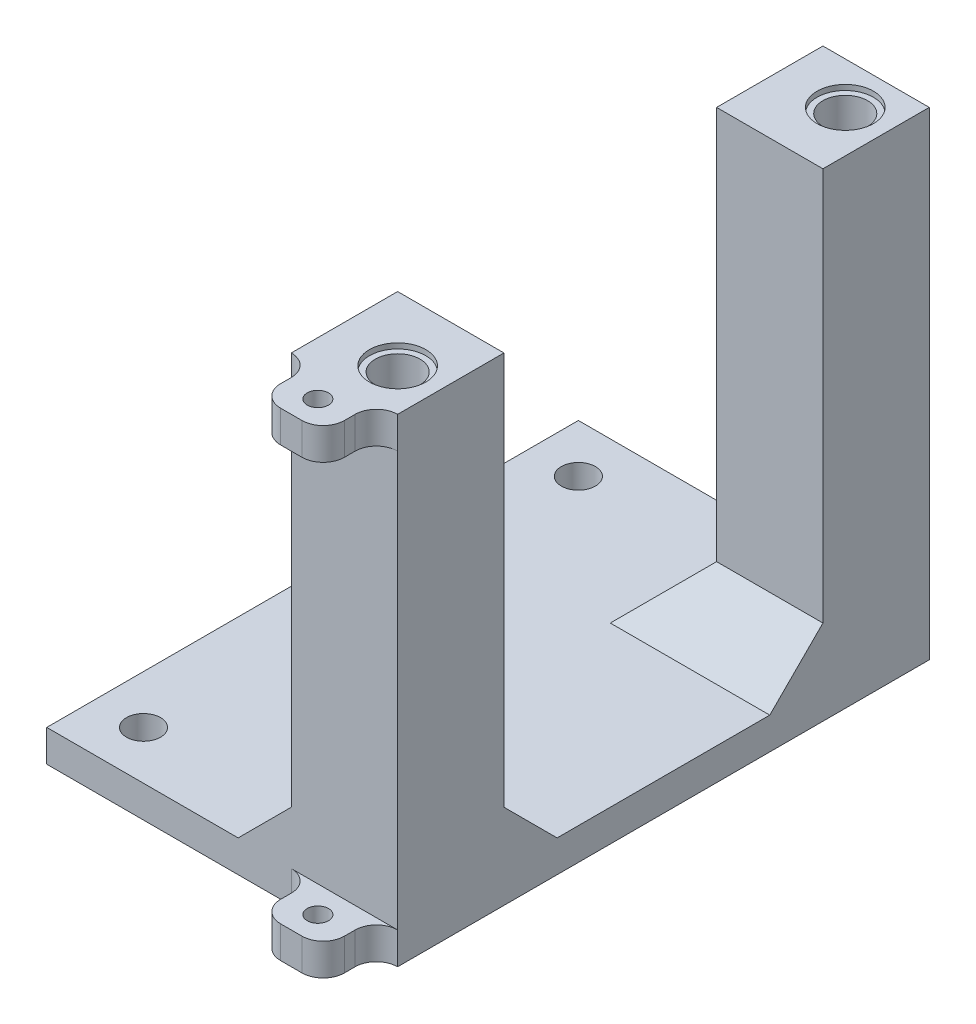
SolidWorks part; units mm, degrees
ref_plane "Front Plane" through (0, 0, 0) normal (0, 0, 1) x (1, 0, 0)
ref_plane "Top Plane" through (0, 0, 0) normal (0, 1, 0) x (1, 0, 0)
ref_plane "Right Plane" through (0, 0, 0) normal (1, 0, 0) x (0, 0, -1)
sketch "Sketch1" plane through (0, 0, 0) normal (0, 1, 0) x (1, 0, 0)
  line L1 (-6.5124, 9.686) -> (1.4876, 9.686)
  line L2 (-6.5124, 9.686) -> (-6.5124, -40.314)
  line L3 (-6.5124, -40.314) -> (1.4876, -40.314)
  line L4 (1.4876, 9.686) -> (1.4876, -40.314)
  line L5 (1.4876, 9.686) -> (26.4876, 9.686)
  line L6 (1.4876, 9.686) -> (1.4876, -40.314)
  line L7 (1.4876, -40.314) -> (26.4876, -40.314)
  line L8 (26.4876, 9.686) -> (26.4876, -40.314)
  circle A0 centre (-1.9624, -35.764) radius 1.6
  circle A1 centre (-1.9624, 5.136) radius 1.6
  dimension "D4" = 3.2
  dimension "D5" = 3.2
  dimension "D6" = 4.55
  dimension "D7" = 4.55
  dimension "D8" = 4.55
  dimension "D9" = 4.55
  dimension "D1" = 8
  dimension "D2" = 50
  dimension "D3" = 25
extrude "Boss-Extrude1" add sketch "Sketch1" along normal blind 3 contours A1 | A0 | L5 L8 L7 L3 L2 L1
sketch "Sketch2" plane through (0, 3, 0) normal (0, 1, 0) x (1, 0, 0)
  line L1 (26.4876, -40.314) -> (16.4876, -40.314)
  line L2 (26.4876, -40.314) -> (26.4876, -30.314)
  line L3 (26.4876, -30.314) -> (16.4876, -30.314)
  line L4 (16.4876, -40.314) -> (16.4876, -30.314)
  line L5 (26.4876, 9.686) -> (16.4876, 9.686)
  line L6 (26.4876, 9.686) -> (26.4876, -0.314)
  line L7 (26.4876, -0.314) -> (16.4876, -0.314)
  line L8 (16.4876, 9.686) -> (16.4876, -0.314)
  dimension "D1" = 10
  dimension "D2" = 10
  dimension "D3" = 10
  dimension "D4" = 10
extrude "Boss-Extrude2" add sketch "Sketch2" along normal blind 42
chamfer "Chamfer1" distance 5 angle 45 4 edges at (16.4876, 3, -4.686) (21.4876, 3, 0.314) (16.4876, 3, 35.314) (21.4876, 3, 30.314)
ref_plane "Plane1" through (0, 45, 0) normal (0, 1, 0) x (1, 0, 0)
sketch "Sketch3" plane through (0, 45, 0) normal (0, 1, 0) x (1, 0, 0)
  line L0 (26.4876, -40.314) -> (26.4876, -30.314) construction
  line L1 (16.4876, -40.314) -> (26.4876, -40.314) construction
  line L2 (26.4876, -0.314) -> (26.4876, 9.686) construction
  line L3 (26.4876, 9.686) -> (16.4876, 9.686) construction
  circle A0 centre (22.5376, -36.364) radius 2.1
  circle A1 centre (22.5376, 5.736) radius 2.1
  dimension "D1" = 4.2
  dimension "D3" = 3.95
  dimension "D4" = 4.2
  dimension "D6" = 3.95
  dimension "D2" = 3.95
  dimension "D5" = 3.95
extrude "Cut-Extrude1" cut sketch "Sketch3" against normal blind 52
sketch "Sketch4" plane through (0, 45, 0) normal (0, 1, 0) x (1, 0, 0)
  circle A0 centre (22.5376, -36.364) radius 2.65
  circle A1 centre (22.5376, 5.736) radius 2.65
  dimension "D1" = 5.3
  dimension "D2" = 5.3
extrude "Cut-Extrude2" cut sketch "Sketch4" against normal blind 0.5
ref_plane "Plane2" through (0, 22.5, 0) normal (0, -1, 0) x (-1, 0, 0)
mirror "Mirror1" about plane through (0, 22.5, 0) normal (0, -1, 0) of "Cut-Extrude2"
sketch "Sketch5" plane through (0, 0, -9.686) normal (0, 0, -1) x (-1, 0, 0)
  line L0 (-22.4876, 36.5) -> (-17.9876, 36.5) construction
  line L1 (-18.2876, 36.2) -> (-22.2399, 36.2)
  line L2 (-18.2876, 36.2) -> (-18.2876, 31.6868)
  line L3 (-18.2876, 31.6868) -> (-22.2399, 31.6868)
  line L4 (-22.2399, 36.2) -> (-22.2399, 31.6868)
  line L5 (-17.9876, 32.25) -> (-17.9876, 37) construction
  dimension "D1" = 0.3
  dimension "D2" = 0.3
sketch "Sketch11" plane through (0, 0, 40.314) normal (0, 0, 1) x (1, 0, 0)
  line L0 (16.4876, 45) -> (26.4876, 45) construction
  line L1 (18.4876, 45) -> (24.4876, 45)
  line L2 (18.4876, 45) -> (18.4876, 42)
  line L3 (18.4876, 42) -> (24.4876, 42)
  line L4 (24.4876, 45) -> (24.4876, 42)
  line L5 (-6.5124, 0) -> (26.4876, 0) construction
  line L6 (18.4876, 0) -> (24.4876, 0)
  line L7 (18.4876, 0) -> (18.4876, 3)
  line L8 (18.4876, 3) -> (24.4876, 3)
  line L9 (24.4876, 0) -> (24.4876, 3)
  line L10 (21.4876, 8) -> (21.4876, 0) construction
  line L11 (21.4876, 8) -> (21.4876, 45) construction
  line L13 (-6.5124, 3) -> (11.4876, 3) construction
  line L14 (16.4876, 8) -> (26.4876, 8) construction
  line L15 (26.4876, 8) -> (39.3241, 4.4212) construction
  line L16 (39.3241, 4.4212) -> (39.5028, 4.4212) construction
  dimension "D1" = 3
  dimension "D2" = 3
  dimension "D3" = 3
  dimension "D4" = 3
  dimension "D5" = 3
extrude "Boss-Extrude7" add sketch "Sketch11" along normal blind 5
sketch "Sketch12" plane through (0, 0, 0) normal (0, -1, 0) x (1, 0, 0)
  line L0 (18.4876, 45.314) -> (24.4876, 40.314) construction
  line L1 (18.4876, 40.314) -> (24.4876, 45.314) construction
  circle A0 centre (21.4876, 42.814) radius 1
  dimension "D1" = 2
extrude "Cut-Extrude5" cut sketch "Sketch12" against normal through all
fillet "Fillet1" radius 2 8 edges at (18.4876, 43.5, 40.314) (18.4876, 43.5, 45.314) (24.4876, 43.5, 45.314) (24.4876, 43.5, 40.314) (24.4876, 1.5, 45.314) (18.4876, 1.5, 45.314) (18.4876, 1.5, 40.314) (24.4876, 1.5, 40.314)
